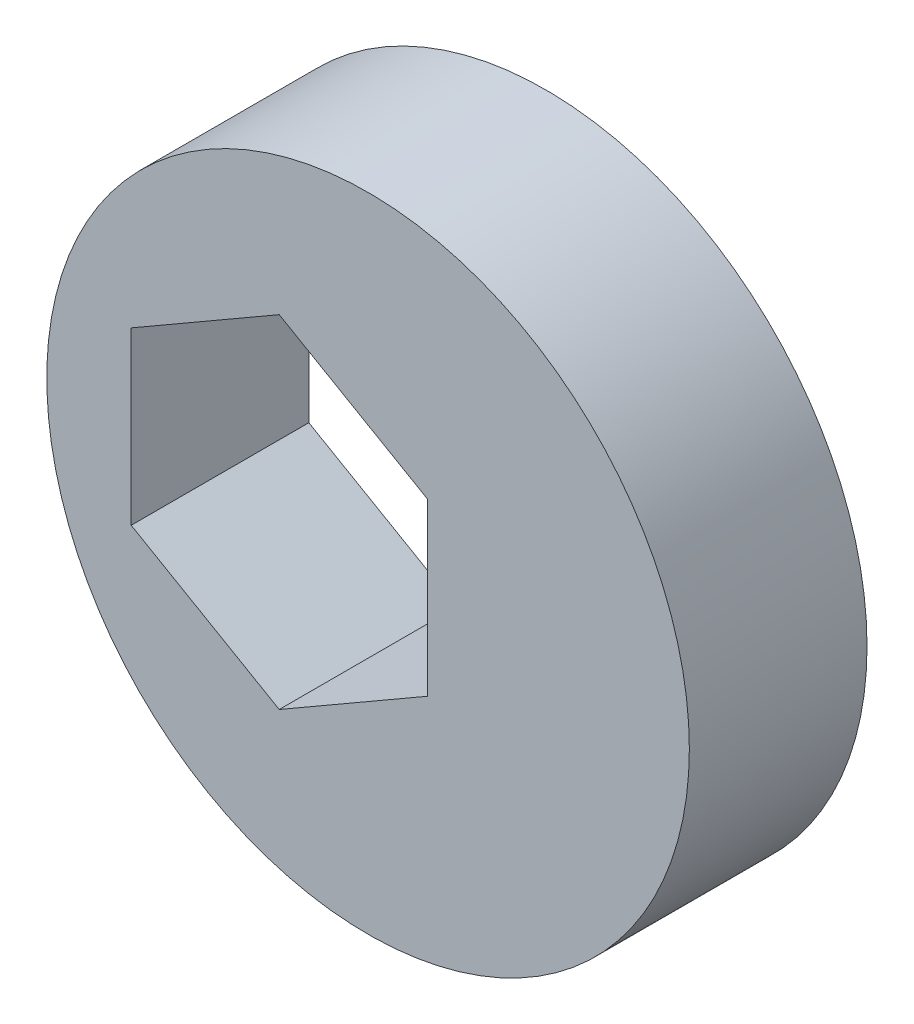
SolidWorks part; units mm, degrees
ref_plane "Front Plane" through (0, 0, 0) normal (0, 0, 1) x (1, 0, 0)
ref_plane "Top Plane" through (0, 0, 0) normal (0, 1, 0) x (1, 0, 0)
ref_plane "Right Plane" through (0, 0, 0) normal (1, 0, 0) x (0, 0, -1)
sketch "Sketch1" plane through (0, 0, 0) normal (0, 0, 1) x (1, 0, 0)
  line L0 (3, 0) -> (0, 0) construction
  line L2 (0, 5.7735) -> (-5, 2.8868)
  line L3 (-5, 2.8868) -> (-5, -2.8868)
  line L4 (-5, -2.8868) -> (0, -5.7735)
  line L5 (0, -5.7735) -> (5, -2.8868)
  line L6 (5, -2.8868) -> (5, 2.8868)
  line L7 (5, 2.8868) -> (0, 5.7735)
  circle A0 centre (3, 0) radius 10.85
  circle A1 centre (0, 0) radius 5 construction
  dimension "D1" = 21.7
  dimension "D2" = 3
  dimension "D3" = 10
extrude "Boss-Extrude1" add sketch "Sketch1" against normal blind 6
ref_axis "Axis1" through (0, 0, 5.6764) along (0, 0, -1)
